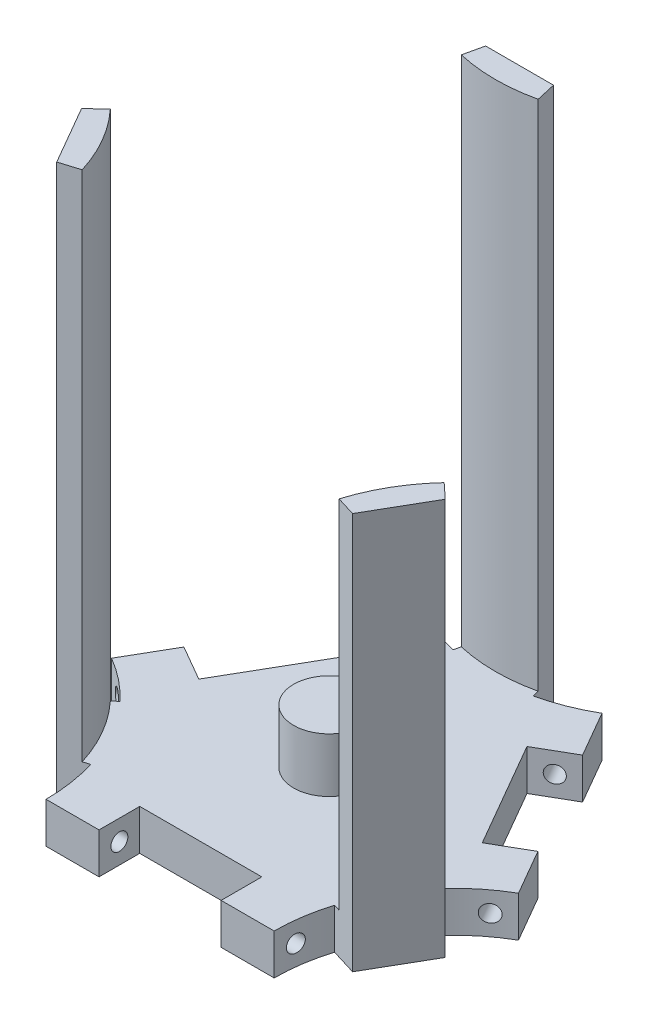
SolidWorks part; units mm, degrees
ref_plane "Front Plane" through (0, 0, 0) normal (0, 0, 1) x (1, 0, 0)
ref_plane "Top Plane" through (0, 0, 0) normal (0, 1, 0) x (1, 0, 0)
ref_plane "Right Plane" through (0, 0, 0) normal (1, 0, 0) x (0, 0, -1)
sketch "Sketch1" plane through (0, 0, 0) normal (0, 1, 0) x (1, 0, 0)
  line L0 (0, 0) -> (43.1834, 0) construction
  line L1 (43.1834, 0) -> (21.5917, 37.3979) construction
  line L2 (21.5917, 37.3979) -> (0, 0) construction
  line L3 (6.5917, 11.4171) -> (15, 25.9808)
  line L4 (28.1834, 25.9808) -> (36.5917, 11.4171)
  line L5 (13.1834, 0) -> (30, 0)
  line L6 (10.7958, 18.6989) -> (21.5917, 12.466) construction
  line L7 (21.5917, 12.466) -> (32.3875, 18.6989) construction
  line L8 (21.5917, 12.466) -> (21.5917, 0) construction
  line L9 (0, 0) -> (21.5917, 12.466) construction
  line L10 (21.5917, 12.466) -> (43.1834, 0) construction
  line L11 (21.5917, 12.466) -> (21.5917, 37.3979) construction
  line L12 (9.6546, 8.9769) -> (8.1898, 7.6152)
  line L13 (12.6016, 3.8727) -> (10.6898, 3.285)
  line L14 (8.1898, 7.6152) -> (10.6898, 3.285)
  line L15 (33.5287, 8.9769) -> (34.9935, 7.6152)
  line L16 (30.5818, 3.8727) -> (32.4935, 3.285)
  line L17 (34.9935, 7.6152) -> (32.4935, 3.285)
  line L18 (18.6448, 24.5483) -> (19.0917, 26.4977)
  line L19 (24.5386, 24.5483) -> (24.0917, 26.4977)
  line L20 (19.0917, 26.4977) -> (24.0917, 26.4977)
  arc A3 (6.5917, 11.4171) -> (9.6546, 8.9769) centre (0.0017, 0.0029) cw
  arc A4 (13.1834, 0) -> (12.6016, 3.8727) centre (0.0034, 0) ccw
  arc A5 (36.5917, 11.4171) -> (33.5287, 8.9769) centre (43.1817, 0.0029) ccw
  arc A6 (30, 0) -> (30.5818, 3.8727) centre (43.18, 0) cw
  arc A7 (15, 25.9808) -> (18.6448, 24.5483) centre (21.59, 37.395) ccw
  arc A8 (28.1834, 25.9808) -> (24.5386, 24.5483) centre (21.5934, 37.395) cw
  point P9 (10.7958, 18.6989)
  point P10 (10.7958, 18.6989)
  point P11 (32.3875, 18.6989)
  point P12 (32.3875, 18.6989)
  point P13 (21.5917, 0)
  point P15 (21.5917, 0)
  point P18 (9.4398, 5.4501)
  point P33 (33.7435, 5.4501)
  point P39 (21.5917, 26.4977)
  dimension "D2" = 13.18
  dimension "D4" = 13.18
  dimension "D5" = 13.18
  dimension "D9" = 13.18
  dimension "D10" = 13.18
  dimension "D14" = 13.18
  dimension "D1" = 30
  dimension "D3" = 16.8166
  dimension "D6" = 2
  dimension "D7" = 2
  dimension "D8" = 5
  dimension "D11" = 2
  dimension "D12" = 2
  dimension "D13" = 5
  dimension "D15" = 2
  dimension "D16" = 2
  dimension "D17" = 60
  dimension "D18" = 5
extrude "Boss-Extrude1" add sketch "Sketch1" along normal blind 3 contours L4 A5 L15 L17 L16 A6 L5 A4 L13 L14 L12 A3 L3 A7 L18 L20 L19 A8
sketch "Sketch2" plane through (0, 3, 0) normal (0, 1, 0) x (1, 0, 0)
  line L0 (21.5917, 0) -> (21.5917, 12.466) construction
  line L1 (13.1834, 0) -> (30, 0) construction
  line L2 (10.7958, 18.6989) -> (21.5917, 12.466) construction
  line L3 (6.5917, 11.4171) -> (15, 25.9808) construction
  line L4 (21.5917, 12.466) -> (32.3875, 18.6989) construction
  line L5 (28.1834, 25.9808) -> (36.5917, 11.4171) construction
  circle A0 centre (21.5917, 12.466) radius 2.625
  dimension "D1" = 5.25
extrude "Boss-Extrude2" add sketch "Sketch2" along normal blind 4
sketch "Sketch3" plane through (0, 0, 0) normal (0, -1, 0) x (1, 0, 0)
  line L0 (17.0917, 0) -> (17.0917, -3)
  line L1 (13.1834, 0) -> (30, 0) construction
  line L2 (17.0917, -3) -> (26.0917, -3)
  line L3 (26.0917, -3) -> (26.0917, 0)
  line L4 (26.0917, 0) -> (17.0917, 0)
  line L5 (6.5917, -11.4171) -> (8.5458, -14.8018) construction
  line L6 (13.0458, -22.5961) -> (15, -25.9808) construction
  line L7 (8.5458, -14.8018) -> (13.0458, -22.5961)
  line L8 (6.5917, -11.4171) -> (15, -25.9808) construction
  line L9 (13.0458, -22.5961) -> (15.6439, -21.0961)
  line L10 (15.6439, -21.0961) -> (11.1439, -13.3018)
  line L11 (11.1439, -13.3018) -> (8.5458, -14.8018)
  line L12 (28.1834, -25.9808) -> (30.1375, -22.5961) construction
  line L13 (34.6375, -14.8018) -> (36.5917, -11.4171) construction
  line L14 (34.6375, -14.8018) -> (32.0394, -13.3018)
  line L15 (28.1834, -25.9808) -> (36.5917, -11.4171) construction
  line L16 (32.0394, -13.3018) -> (27.5394, -21.0961)
  line L17 (27.5394, -21.0961) -> (30.1375, -22.5961)
  line L18 (30.1375, -22.5961) -> (34.6375, -14.8018)
  line L19 (17.0917, 0) -> (13.1834, 0) construction
  line L20 (26.0917, 0) -> (30, 0) construction
  dimension "D1" = 9
  dimension "D2" = 3
  dimension "D3" = 9
  dimension "D4" = 3
  dimension "D5" = 9
  dimension "D6" = 3
extrude "Cut-Extrude1" cut sketch "Sketch3" against normal through all
sketch "Sketch4" plane through (2.25, 0, 3.8971) normal (-0.5, 0, -0.866) x (-0.866, 0, 0.5)
  line L0 (-34.3979, 3) -> (-37.3979, 3) construction
  line L1 (-37.3979, 3) -> (-37.3979, 0) construction
  circle A0 centre (-35.8979, 1.5) radius 0.625
  dimension "D1" = 1.25
  dimension "D2" = 1.5
  dimension "D3" = 1.5
extrude "Cut-Extrude2" cut sketch "Sketch4" against normal through all and the other way through all
sketch "Sketch5" plane through (8.5458, 0, -14.8018) normal (0.5, 0, -0.866) x (-0.866, 0, -0.5)
  line L0 (-3, 0) -> (0, 0) construction
  line L1 (0, 3) -> (0, 0) construction
  circle A0 centre (-1.5, 1.5) radius 0.625
  dimension "D1" = 1.25
  dimension "D2" = 1.5
  dimension "D3" = 1.5
extrude "Cut-Extrude3" cut sketch "Sketch5" against normal through all and the other way through all
sketch "Sketch6" plane through (26.0917, 0, 0) normal (-1, 0, 0) x (0, 0, 1)
  line L0 (0, 3) -> (-3, 3) construction
  line L1 (0, 3) -> (0, 0) construction
  circle A0 centre (-1.5, 1.5) radius 0.625
  dimension "D1" = 1.25
  dimension "D2" = 1.5
  dimension "D3" = 1.5
extrude "Cut-Extrude4" cut sketch "Sketch6" against normal through all and the other way through all
sketch "Sketch7" plane through (0, 3, 0) normal (0, 1, 0) x (1, 0, 0)
  line L1 (8.1898, 7.6152) -> (10.6898, 3.285)
  line L4 (32.4935, 3.285) -> (34.9935, 7.6152)
  line L7 (19.0917, 26.4977) -> (24.0917, 26.4977)
  line L9 (19.0917, 26.4977) -> (18.7565, 25.0356)
  line L10 (18.6448, 24.5483) -> (19.0917, 26.4977) construction
  line L11 (24.0917, 26.4977) -> (24.4269, 25.0356)
  line L12 (24.5386, 24.5483) -> (24.0917, 26.4977) construction
  line L13 (8.1898, 7.6152) -> (9.2884, 8.6365)
  line L14 (9.6546, 8.9769) -> (8.1898, 7.6152) construction
  line L15 (10.6898, 3.285) -> (12.1236, 3.7258)
  line L16 (12.6016, 3.8727) -> (10.6898, 3.285) construction
  line L17 (34.9935, 7.6152) -> (33.8949, 8.6365)
  line L18 (33.5287, 8.9769) -> (34.9935, 7.6152) construction
  line L19 (32.4935, 3.285) -> (31.0597, 3.7258)
  line L20 (30.5818, 3.8727) -> (32.4935, 3.285) construction
  arc A3 (18.7565, 25.0356) -> (24.4269, 25.0356) centre (21.5917, 37.4023) ccw
  arc A4 (33.8949, 8.6365) -> (31.0597, 3.7258) centre (43.1872, -0.0022) ccw
  arc A5 (9.2884, 8.6365) -> (12.1236, 3.7258) centre (-0.0038, -0.0022) cw
  dimension "D1" = 1.5
  dimension "D2" = 1.5
  dimension "D3" = 1.5
  dimension "D4" = 1.5
  dimension "D5" = 1.5
  dimension "D6" = 1.5
extrude "Boss-Extrude3" add sketch "Sketch7" along normal blind 26.25
scale "Scale1" scale about centroid uniform scaling yes scale factor 1.3
sketch "Sketch10" plane through (0, 36.1405, 0) normal (0, 1, 0) x (1, 0, 0)
  line L0 (17.9059, 28.8065) -> (18.3417, 30.7072)
  line L1 (18.3417, 30.7072) -> (24.8417, 30.7072)
  line L2 (24.8417, 30.7072) -> (25.2774, 28.8065)
  line L3 (5.5975, 7.4876) -> (4.1693, 6.1599)
  line L4 (4.1693, 6.1599) -> (7.4193, 0.5308)
  line L5 (7.4193, 0.5308) -> (9.2832, 1.1037)
  arc A0 (17.9059, 28.8065) -> (25.2774, 28.8065) centre (21.5917, 44.8832) ccw
  arc A1 (5.5975, 7.4876) -> (9.2832, 1.1037) centre (-6.4825, -3.7427) cw
extrude "Boss-Extrude5" add sketch "Sketch10" along normal blind 15
